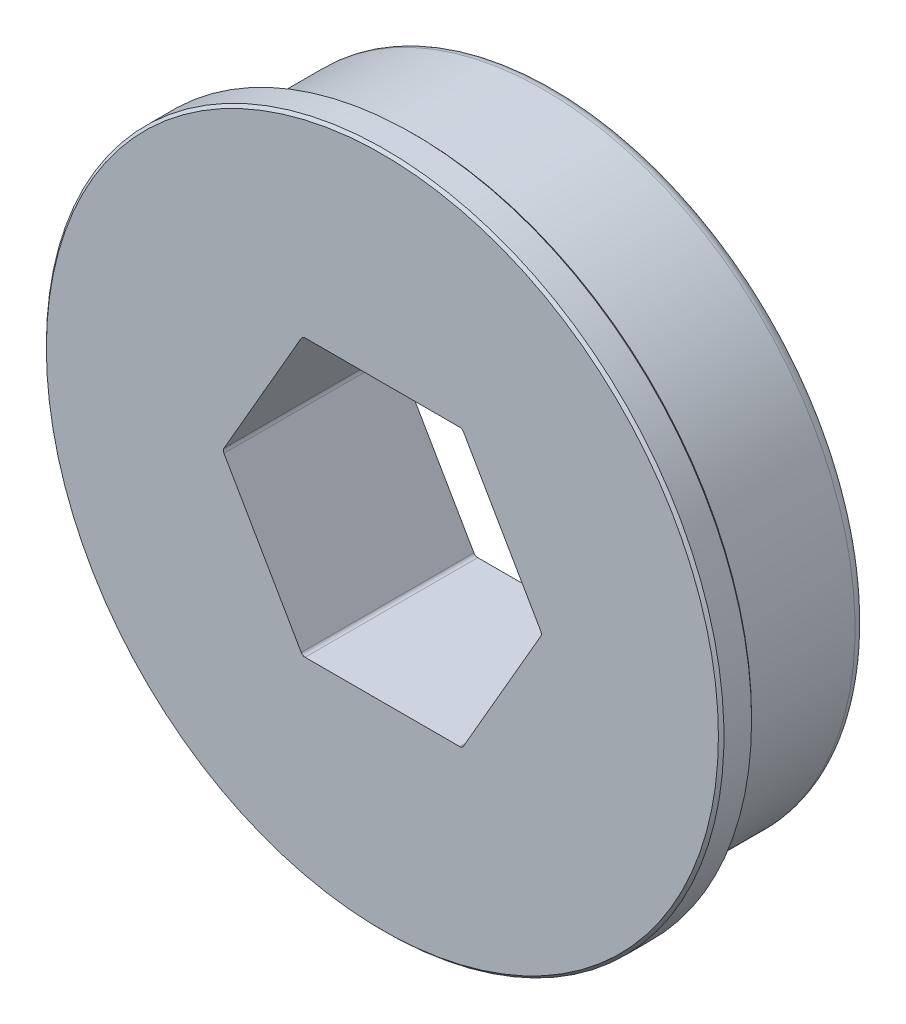
SolidWorks part; units mm, degrees
material "Plain Carbon Steel"
ref_plane "Front Plane" through (0, 0, 0) normal (0, 0, 1) x (1, 0, 0)
ref_plane "Top Plane" through (0, 0, 0) normal (0, 1, 0) x (1, 0, 0)
ref_plane "Right Plane" through (0, 0, 0) normal (1, 0, 0) x (0, 0, -1)
ref_plane "Plane1" through (0, 0, 6.4033) normal (0, 0, -1) x (-1, 0, 0)
sketch "Sketch1" plane through (0, 0, 6.4033) normal (0, 0, -1) x (-1, 0, 0)
  circle A0 centre (0, 0) radius 15.5575
extrude "Boss-Extrude1" add sketch "Sketch1" against normal blind 1.524
sketch "Sketch2" plane through (0, 0, 6.4033) normal (0, 0, -1) x (-1, 0, 0)
  circle A0 centre (0, 0) radius 13.97
extrude "Boss-Extrude2" add sketch "Sketch2" along normal blind 0.508
ref_plane "Plane2" through (0, 0, 5.8953) normal (0, 0, 1) x (1, 0, 0)
sketch "Sketch3" plane through (0, 0, 5.8953) normal (0, 0, 1) x (1, 0, 0)
  circle A0 centre (0, 0) radius 14.2875
extrude "Boss-Extrude3" add sketch "Sketch3" against normal blind 5.8953
sketch "Sketch4" plane through (0, 0, 7.9273) normal (0, 0, 1) x (1, 0, 0)
  line L0 (7.3323, 0) -> (3.6662, 6.35)
  line L1 (3.6662, 6.35) -> (-3.6662, 6.35)
  line L2 (-3.6662, 6.35) -> (-7.3323, 0)
  line L3 (-7.3323, 0) -> (-3.6662, -6.35)
  line L4 (-3.6662, -6.35) -> (3.6662, -6.35)
  line L5 (3.6662, -6.35) -> (7.3323, 0)
extrude "Cut-Extrude1" cut sketch "Sketch4" against normal through all
chamfer "Chamfer1" distance 0.127 angle 45 1 edges at (15.5575, 0, 7.9273)
chamfer "Chamfer2" distance 0.127 angle 45 1 edges at (15.5575, 0, 6.4033)
fillet "Fillet1" radius 0.2032 6 edges at (7.3323, 0, 3.9637) (3.6662, 6.35, 3.9637) (-3.6662, -6.35, 3.9637) (3.6662, -6.35, 3.9637) (-7.3323, 0, 3.9637) (-3.6662, 6.35, 3.9637) tangent propagation no
fillet "Fillet2" radius 0.508 1 edges at (-14.2875, 0, 0) tangent propagation no
